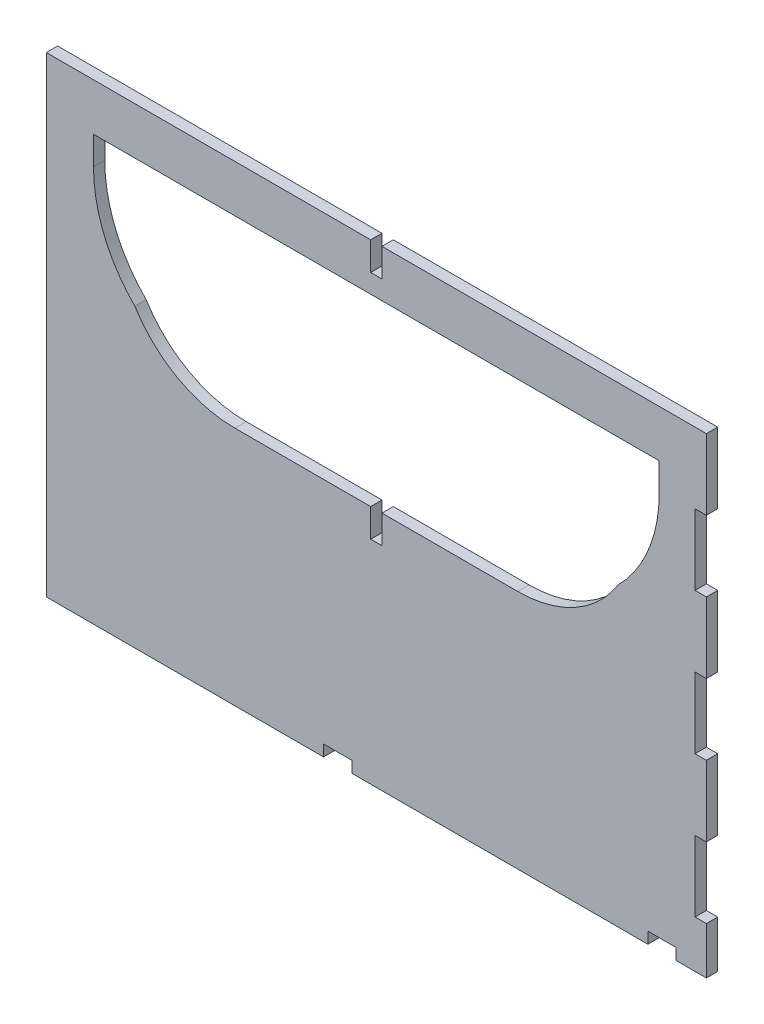
SolidWorks part; units mm, degrees
ref_plane "Front" through (0, 0, 0) normal (0, 0, 1) x (1, 0, 0)
ref_plane "Top" through (0, 0, 0) normal (0, 1, 0) x (1, 0, 0)
ref_plane "Right" through (0, 0, 0) normal (1, 0, 0) x (0, 0, -1)
sketch "Sketch1" plane through (0, 0, 0) normal (0, 0, 1) x (1, 0, 0)
  line L1 (0, 0) -> (-200, 0)
  line L2 (0, 0) -> (0, 150)
  line L4 (-200, 0) -> (-200, 150)
  line L5 (-100, 90) -> (-100, 0) construction
  line L6 (-175, 110) -> (-175, 125)
  line L7 (-25, 110) -> (-25, 125)
  line L9 (-175, 125) -> (-25, 125)
  line L11 (-200, 150) -> (0, 150)
  arc A0 (-153.0972, 57.0313) -> (-46.9028, 57.0312) centre (-100, 90) ccw
  arc A1 (-175, 110) -> (-153.0972, 57.0313) centre (-100, 110) ccw
  arc A2 (-46.9028, 57.0312) -> (-25, 110) centre (-100, 110) ccw
  dimension "D3" = 62.5
  dimension "D4" = 75
  dimension "D1" = 200
  dimension "D2" = 25
  dimension "D5" = 20
  dimension "D6" = 90
  dimension "D7" = 150
extrude "Boss-Extrude1" add sketch "Sketch1" along normal blind 6
sketch "Sketch3" plane through (0, 0, 6) normal (0, 0, 1) x (1, 0, 0)
  line L0 (-200, 150) -> (-200, 0) construction
  line L1 (-100, 27.5) -> (-200, 27.5)
  line L2 (-100, 27.5) -> (-100, 125)
  line L3 (-100, 125) -> (-200, 125)
  line L4 (-200, 27.5) -> (-200, 125)
  line L7 (-25, 125) -> (-175, 125) construction
  arc A0 (-153.0972, 57.0313) -> (-46.9028, 57.0312) centre (-100, 90) ccw construction
extrude "Cut-Extrude1" cut sketch "Sketch3" against normal blind 6
sketch "Sketch4" plane through (0, 0, 6) normal (0, 0, 1) x (1, 0, 0)
  line L0 (-250, 110) -> (-100, 110) construction
  line L1 (-100, 90) -> (-250, 90) construction
  line L2 (-250, 90) -> (-250, 110) construction
  line L3 (-25, 125) -> (0, 125) construction
  line L4 (-200, 27.5) -> (-250, 27.5)
  line L5 (-200, 27.5) -> (-200, 0)
  line L6 (-200, 0) -> (-350, 0)
  line L9 (-350, 0) -> (-350, 150)
  line L11 (-325, 110) -> (-325, 125)
  line L12 (-200, 125) -> (-325, 125)
  line L13 (-200, 125) -> (-200, 150)
  line L14 (-200, 150) -> (-350, 150)
  line L16 (0, 0) -> (0, 150) construction
  line L17 (-325, 125) -> (-350, 125) construction
  line L18 (-200, 0) -> (0, 0) construction
  arc A0 (-325, 110) -> (-303.0972, 57.0312) centre (-250, 110) ccw
  circle A1 centre (-100, 90) radius 62.5 construction
  circle A2 centre (-100, 110) radius 75 construction
  arc A3 (-46.9028, 57.0312) -> (-25, 110) centre (-100, 110) ccw construction
  arc A4 (-100, 27.5) -> (-46.9028, 57.0312) centre (-100, 90) ccw construction
  arc A5 (-303.0972, 57.0312) -> (-250, 27.5) centre (-250, 90) ccw
  dimension "D1" = 150
  dimension "D2" = 125
  dimension "D4" = 125
  dimension "D3" = 150
extrude "Boss-Extrude3" add sketch "Sketch4" against normal blind 6
sketch "Sketch5" plane through (0, 0, 6) normal (0, 0, 1) x (1, 0, 0)
  line L1 (-178, 150) -> (-172, 150)
  line L2 (-178, 150) -> (-178, 135)
  line L3 (-178, 135) -> (-172, 135)
  line L4 (-172, 150) -> (-172, 135)
  line L5 (-250, 27.5) -> (-100, 27.5) construction
  line L6 (-178, 27.5) -> (-172, 27.5)
  line L7 (-178, 27.5) -> (-178, 12.5)
  line L8 (-178, 12.5) -> (-172, 12.5)
  line L9 (-172, 27.5) -> (-172, 12.5)
  line L10 (0, 150) -> (-350, 150) construction
  point P12 (-175, 150)
  point P14 (-175, 150)
  dimension "D1" = 6
  dimension "D2" = 15
extrude "Cut-Extrude2" cut sketch "Sketch5" against normal blind 6
sketch "Sketch6" plane through (0, 0, 6) normal (0, 0, 1) x (1, 0, 0)
  line L0 (0, 0) -> (0, 150) construction
  line L1 (0, 112.5) -> (-6, 112.5)
  line L2 (0, 112.5) -> (0, 75)
  line L3 (0, 75) -> (-6, 75)
  line L4 (-6, 112.5) -> (-6, 75)
  line L5 (0, 150) -> (-172, 150) construction
  dimension "D1" = 37.5
  dimension "6" = 6
  dimension "D2" = 37.5
extrude "Cut-Extrude3" cut sketch "Sketch6" against normal blind 6
sketch "Sketch8" plane through (0, 0, 6) normal (0, 0, 1) x (1, 0, 0)
  line L1 (-350, 0) -> (0, 0)
  line L2 (-350, 0) -> (-350, -100)
  line L3 (-350, -100) -> (0, -100)
  line L4 (0, 0) -> (0, -100)
  point P5 (0, 0)
  dimension "D1" = 100
extrude "Boss-Extrude4" add sketch "Sketch8" against normal up to surface (6 mm away) up to face at (-117.6667, 103.75, 0)
pattern_linear "LPattern1" count 3 spacing 75 along (0, -1, 0) of "Cut-Extrude3"
sketch "Sketch7" plane through (0, 0, 6) normal (0, 0, 1) x (1, 0, 0)
  line L1 (-16, -100) -> (-31, -100)
  line L2 (-16, -100) -> (-16, -94)
  line L3 (-16, -94) -> (-31, -94)
  line L4 (-31, -100) -> (-31, -94)
  line L5 (-6, -37.5) -> (-6, -75) construction
  line L6 (-350, -100) -> (0, -100) construction
  line L7 (-178, 27.5) -> (-178, 12.5) construction
  line L8 (-188, -100) -> (-203, -100)
  line L9 (-188, -100) -> (-188, -94)
  line L10 (-188, -94) -> (-203, -94)
  line L11 (-203, -100) -> (-203, -94)
  dimension "D1" = 15
  dimension "D2" = 10
  dimension "D3" = 6
  dimension "D4" = 10
extrude "s" cut sketch "Sketch7" against normal through all
